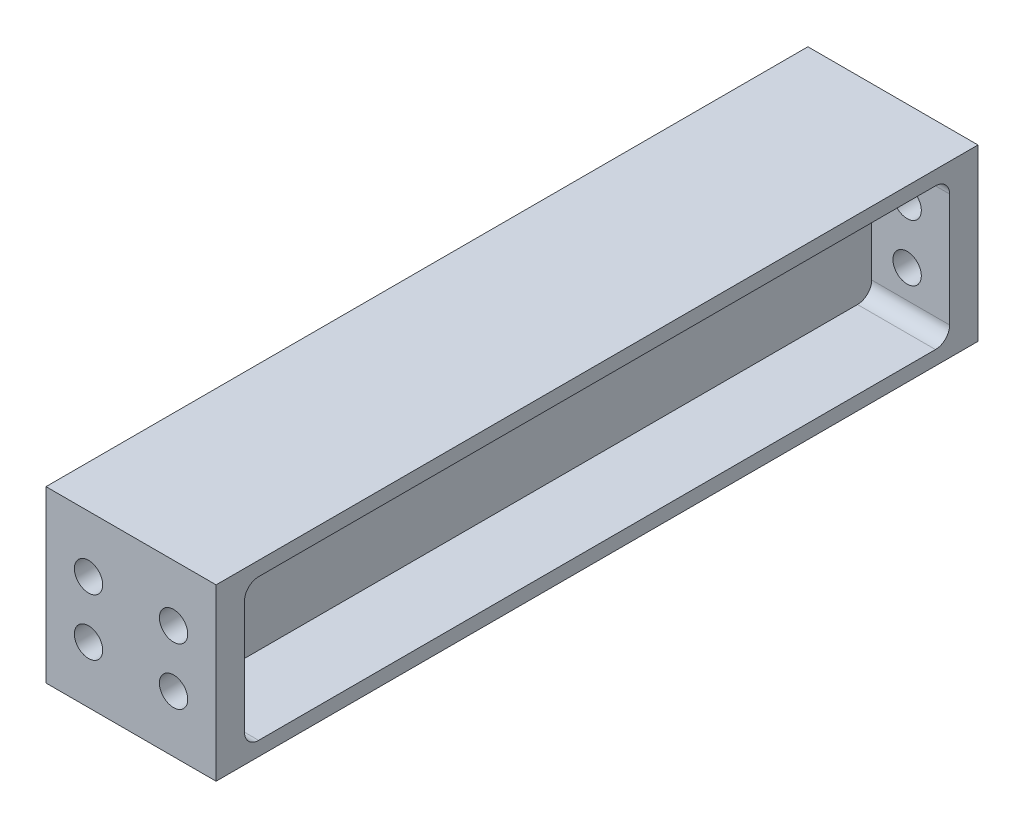
SolidWorks part; units mm, degrees
material "6061 Alloy"
ref_plane "Front Plane" through (0, 0, 0) normal (0, 0, 1) x (1, 0, 0)
ref_plane "Top Plane" through (0, 0, 0) normal (0, 1, 0) x (1, 0, 0)
ref_plane "Right Plane" through (0, 0, 0) normal (1, 0, 0) x (0, 0, -1)
sketch "Sketch2" plane through (0, 0, 0) normal (0, 0, 1) x (1, 0, 0)
  line L1 (0, 0) -> (38.1, 0)
  line L2 (0, 0) -> (0, 38.1)
  line L3 (0, 38.1) -> (38.1, 38.1)
  line L4 (38.1, 0) -> (38.1, 38.1)
  dimension "D1" = 38.1
extrude "Boss-Extrude1" add sketch "Sketch2" along normal up to surface (170.6561 mm away)
ref_plane "Plane1" through (19.05, 0, 0) normal (1, 0, 0) x (0, 0, -1)
sketch "Sketch3" plane through (38.1, 0, 0) normal (1, 0, 0) x (0, 0, -1)
  line L4 (-85.328, 34.925) -> (-85.328, 38.1) construction
  line L5 (-164.3061, 34.925) -> (-6.35, 34.925)
  line L6 (-164.3061, 34.925) -> (-164.3061, 3.175)
  line L7 (-164.3061, 3.175) -> (-6.35, 3.175)
  line L8 (-6.35, 34.925) -> (-6.35, 3.175)
  line L9 (-170.6561, 38.1) -> (0, 38.1) construction
  line L10 (-6.35, 19.05) -> (0, 19.05) construction
  line L11 (0, 0) -> (0, 38.1) construction
  dimension "D1" = 6.35
  dimension "D2" = 3.175
extrude "Cut-Extrude1" cut sketch "Sketch3" against normal blind 17.4625
fillet "Fillet1" radius 3.175 4 edges at (29.3688, 3.175, 6.35) (29.3688, 3.175, 164.3061) (29.3688, 34.925, 164.3061) (29.3688, 34.925, 6.35)
mirror "Mirror1" about plane through (19.05, 0, 0) normal (1, 0, 0) of "Fillet1", "Cut-Extrude1"
hole_wizard "1/4 (0.25) Diameter Hole1" positions "Sketch5" profile "Sketch6" hole size "1/4" standard "ANSI Inch" end condition through all
sketch "Sketch5" plane through (0, 0, 0) normal (0, 0, -1) x (-1, 0, 0)
  line L0 (0, 38.1) -> (0, 0) construction
  line L1 (-38.1, 0) -> (-38.1, 38.1) construction
  line L2 (-38.1, 38.1) -> (0, 38.1) construction
  line L3 (0, 0) -> (-38.1, 0) construction
  point P0 (-9.525, 25.4)
  point P2 (-9.525, 12.7)
  point P4 (-28.575, 12.7)
  point P6 (-28.575, 25.4)
  dimension "D1" = 9.525
  dimension "D2" = 9.525
  dimension "D3" = 12.7
  dimension "D4" = 12.7
sketch "Sketch6" plane through (9.525, 25.4, 0) normal (1, 0, 0) x (0, 1, 0)
  line L0 (0, 0) -> (0, 170.6561)
  line L1 (0, 170.6561) -> (3.175, 170.6561)
  line L2 (3.175, 170.6561) -> (3.175, 0)
  line L5 (3.175, 0) -> (0, 0)
  line L11 (0, -6.35) -> (0, 107.95) construction
  dimension "Thru Hole Dia." = 6.35
  dimension "Thru Hole Depth" = 170.6561
